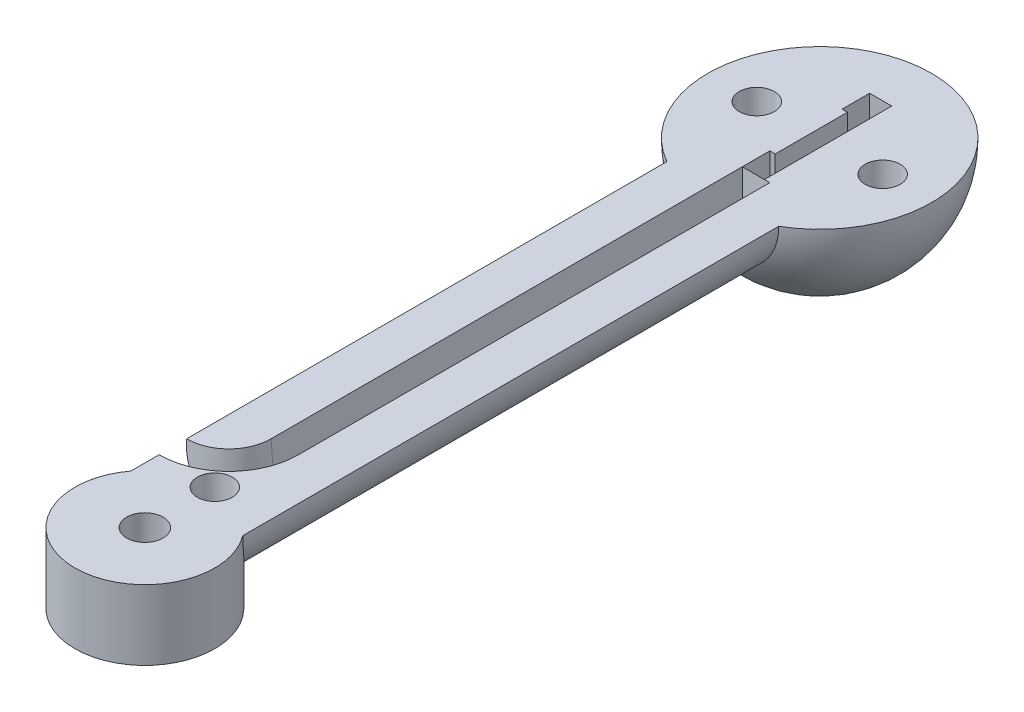
SolidWorks part; units mm, degrees
ref_plane "Front Plane" through (0, 0, 0) normal (0, 0, 1) x (1, 0, 0)
ref_plane "Top Plane" through (0, 0, 0) normal (0, 1, 0) x (1, 0, 0)
ref_plane "Right Plane" through (0, 0, 0) normal (1, 0, 0) x (0, 0, -1)
sketch "Sketch1" plane through (0, 0, 0) normal (0, 0, 1) x (1, 0, 0)
  circle A0 centre (0, 0) radius 10.16
  dimension "D1" = 20.32
extrude "Boss-Extrude1" add sketch "Sketch1" along normal blind 101.6
sketch "Sketch2" plane through (0, 0, 0) normal (1, 0, 0) x (0, 0, -1)
  line L0 (55, 0) -> (-55, 0) construction
  line L1 (-2.7224, 0) -> (37.9176, 0)
  circle A0 centre (17.5976, 0) radius 20.32
  dimension "D1" = 40.64
revolve "Revolve1" add sketch "Sketch2" angle 360 about L1 region at (0, 8.6241, -17.5976)
sketch "Sketch3" plane through (0, 0, 0) normal (0, 1, 0) x (1, 0, 0)
  line L0 (0, -22.352) -> (0, 22.352) construction
  line L1 (-10.16, -101.6) -> (10.16, -101.6) construction
  circle A0 centre (0, -104.902) radius 12.7
  circle A1 centre (0, -104.902) radius 3.302
  dimension "D1" = 6.604
  dimension "D2" = 25.4
extrude "Boss-Extrude2" add sketch "Sketch3" along normal mid plane 25.4
sketch "Sketch5" plane through (0, 0, 0) normal (0, 1, 0) x (1, 0, 0)
  line L1 (-24.3212, 47.5698) -> (26.0069, 47.5698)
  line L2 (-24.3212, 47.5698) -> (-24.3212, -130.1438)
  line L3 (-24.3212, -130.1438) -> (26.0069, -130.1438)
  line L4 (26.0069, 47.5698) -> (26.0069, -130.1438)
  line L5 (-24.3212, 47.5698) -> (26.0069, -130.1438) construction
  line L6 (-24.3212, -130.1438) -> (26.0069, 47.5698) construction
  point P4 (0.8428, -41.287)
extrude "Cut-Extrude2" cut sketch "Sketch5" along normal through all
sketch "Sketch4" plane through (0, 0, 0) normal (0, 1, 0) x (1, 0, 0)
  line L0 (-10.16, -87.162) -> (-10.16, -92.162)
  line L1 (-1.524, 29.1546) -> (1.524, 29.1546)
  line L2 (-1.524, 29.1546) -> (-1.524, 6.0406)
  line L4 (1.524, 29.1546) -> (1.524, 6.0406)
  line L5 (-1.524, 29.1546) -> (1.524, 6.0406) construction
  line L6 (-1.524, 6.0406) -> (1.524, 29.1546) construction
  line L7 (2.5, 6.0406) -> (-2.5, 6.0406)
  line L8 (2.5, 6.0406) -> (2.5, -79.502)
  line L9 (2.5, -79.502) -> (-2.5, -79.502)
  line L10 (-2.5, 6.0406) -> (-2.5, -79.502)
  line L11 (-10.16, 0) -> (-10.16, -97.282) construction
  line L12 (-15.16, -92.162) -> (-10.16, -92.162) construction
  line L14 (0, -11.5708) -> (0, 11.5708) construction
  line L15 (0, -79.502) -> (0, -104.902) construction
  line L19 (-2.5, 6.0406) -> (-2.5, 11.0406)
  line L20 (-2.5, 11.0406) -> (-1.524, 11.0406)
  line L22 (-2.5, 6.0406) -> (-1.524, 11.0406) construction
  line L23 (-2.5, 11.0406) -> (-1.524, 6.0406) construction
  line L24 (-1.524, 29.1546) -> (-2.5, 29.1546)
  line L26 (-1.524, 24.1546) -> (-2.5, 24.1546)
  line L27 (-2.5, 29.1546) -> (-2.5, 24.1546)
  line L28 (-1.524, 29.1546) -> (-2.5, 24.1546) construction
  line L29 (-1.524, 24.1546) -> (-2.5, 29.1546) construction
  arc A0 (2.5, -79.502) -> (-10.16, -92.162) centre (-10.16, -79.502) cw
  arc A1 (-10.16, -87.162) -> (-2.5, -79.502) centre (-10.16, -79.502) ccw
  circle A2 centre (-11.43, 17.5976) radius 3.175
  circle A3 centre (11.43, 17.5976) radius 3.175
  circle A4 centre (0, -92.202) radius 3.175
  circle A5 centre (0, 17.5976) radius 20.32 construction
  arc A6 (10.16, 0) -> (-10.16, 0) centre (0, 17.5976) ccw construction
  arc A7 (-10.16, -97.282) -> (10.16, -97.282) centre (0, -104.902) ccw construction
  circle A8 centre (0, -104.902) radius 3.302 construction
  point P4 (0, 17.5976)
  point P9 (0, -37.3022)
  point P20 (0, -79.502)
  point P34 (0, -104.902)
  point P39 (0, -104.902)
  point P40 (-2.012, 26.6546)
  point P45 (0, -92.202)
  point P52 (-2.012, 8.5406)
  dimension "D3" = 6.35
  dimension "D1" = 3.048
  dimension "D2" = 23.114
  dimension "D4" = 11.43
  dimension "D5" = 11.43
  dimension "D6" = 5
extrude "Cut-Extrude3" cut sketch "Sketch4" against normal blind 11.684
extrude "Cut-Extrude4" cut sketch "Sketch4<3>" against normal blind 6.35 draft 5 contours A3 | A1 L0 A0 L9 | A4 | L7 L10 L9 L8 | A2 region at (-3.5614, 0, 86.1006) region at (0, 0, 36.7307) region at (11.43, 0, -17.5976) region at (0, 0, 92.202)
sketch "Sketch4<3>" plane through (0, 0, 0) normal (0, 1, 0) x (1, 0, 0) same geometry as "Sketch4"
sketch "Sketch7" plane through (-10.0828, -0.8821, 0) normal (0.9962, 0.0872, 0) x (0, 0, -1)
  line L0 (-92.0067, -0.8855) -> (-92.162, 0.8855)
  line L1 (-92.162, 0.8855) -> (-97.282, 0.8855) construction
  line L2 (-92.162, 0.8855) -> (-87.162, 0.8855)
  line L3 (-87.162, 0.8855) -> (-87.3148, -0.8855)
  line L4 (-87.3148, -0.8855) -> (-92.0067, -0.8855)
extrude "Cut-Extrude5" cut sketch "Sketch7" against normal through all
